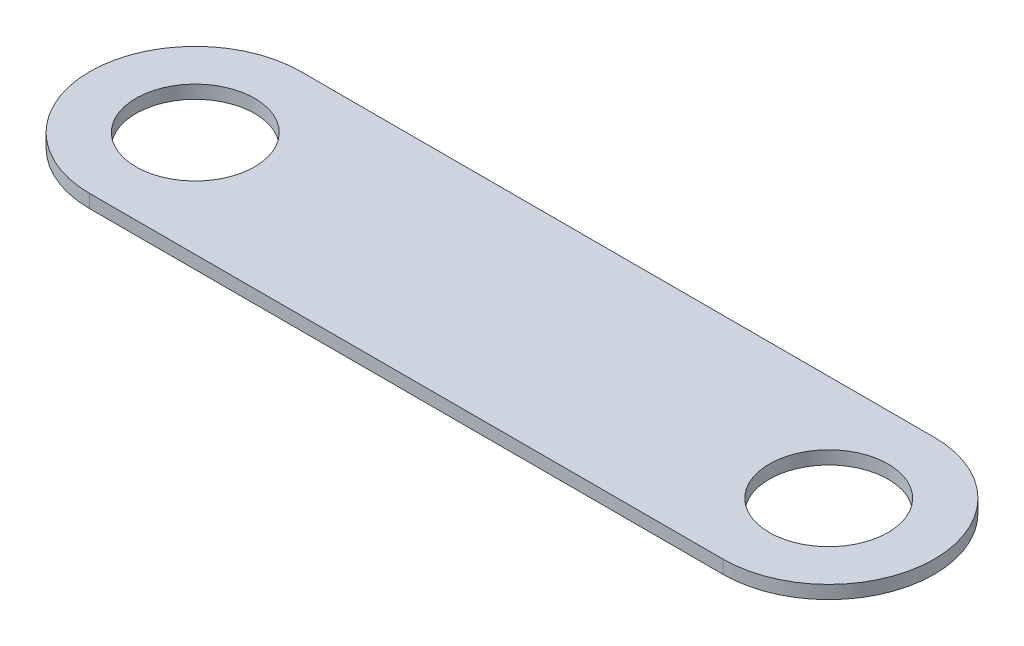
SolidWorks part; units mm, degrees
ref_plane "Front" through (0, 0, 0) normal (0, 0, 1) x (1, 0, 0)
ref_plane "Top" through (0, 0, 0) normal (0, 1, 0) x (1, 0, 0)
ref_plane "Right" through (0, 0, 0) normal (1, 0, 0) x (0, 0, -1)
sketch "Sketch1" plane through (0, 0, 0) normal (0, 1, 0) x (1, 0, 0)
  line L0 (0, 0) -> (152.4, 0) construction
  line L1 (0, 0) -> (152.4, 0) construction
  line L2 (0, 25.4) -> (152.4, 25.4)
  line L3 (0, -25.4) -> (152.4, -25.4)
  circle A0 centre (0, 0) radius 14.2875
  circle A1 centre (152.4, 0) radius 14.2875
  arc A2 (0, 25.4) -> (0, -25.4) centre (0, 0) ccw
  arc A3 (152.4, -25.4) -> (152.4, 25.4) centre (152.4, 0) ccw
  point P5 (76.2, 0)
  point P10 (76.2, -25.4)
  dimension "D1" = 28.575
  dimension "D2" = 28.575
  dimension "D3" = 152.4
  dimension "D4" = 50.8
extrude "Boss-Extrude1" add sketch "Sketch1" along normal blind 3.175
